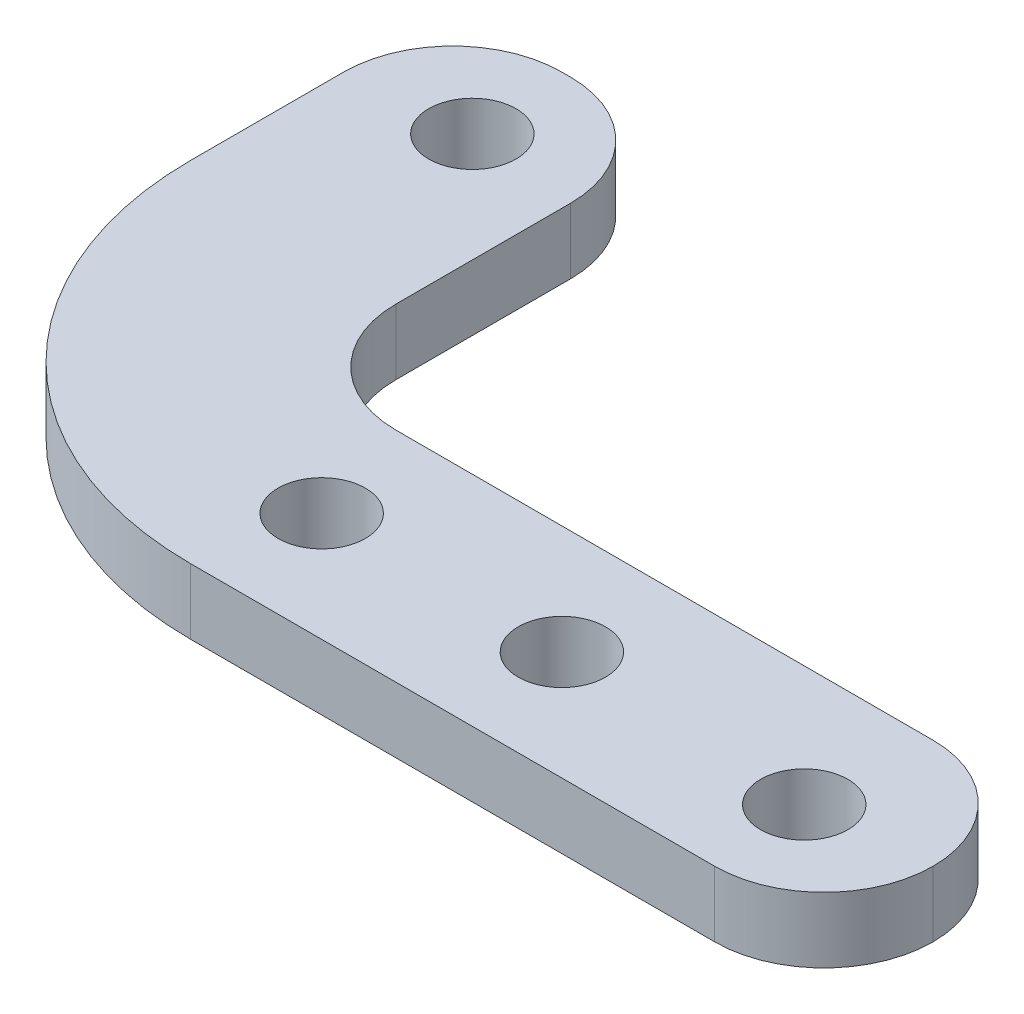
SolidWorks part; units mm, degrees
material "ABS PC"
ref_plane "Front Plane" through (0, 0, 0) normal (0, 0, 1) x (1, 0, 0)
ref_plane "Top Plane" through (0, 0, 0) normal (0, 1, 0) x (1, 0, 0)
ref_plane "Right Plane" through (0, 0, 0) normal (1, 0, 0) x (0, 0, -1)
sketch "Sketch1" plane through (0, 0, 0) normal (0, 1, 0) x (1, 0, 0)
  line L1 (22.5, -14) -> (-22.5, -14)
  line L2 (22.5, -14) -> (22.5, 14)
  line L3 (22.5, 14) -> (-22.5, 14)
  line L4 (-22.5, -14) -> (-22.5, 14)
  line L5 (22.5, -14) -> (-22.5, 14) construction
  line L6 (22.5, 14) -> (-22.5, -14) construction
  point P0 (0, 0)
  dimension "D1" = 28
  dimension "D2" = 45
extrude "Boss-Extrude1" add sketch "Sketch1" along normal blind 3
hole_wizard "Ø4.0 (4) Diameter Hole1" positions "Sketch2" profile "Sketch3" hole size "Ø4.0" standard "ANSI Metric" end condition through all
sketch "Sketch2" plane through (0, 3, 0) normal (0, 1, 0) x (1, 0, 0)
  line L1 (17.1, -9.5) -> (-17.1, -9.5)
  line L2 (17.1, -9.5) -> (17.1, 9.5)
  line L3 (17.1, 9.5) -> (-17.1, 9.5)
  line L4 (-17.1, -9.5) -> (-17.1, 9.5)
  line L5 (17.1, -9.5) -> (-17.1, 9.5) construction
  line L6 (17.1, 9.5) -> (-17.1, -9.5) construction
  line L7 (0, 14) -> (0, 0) construction
  line L8 (22.5, 14) -> (-22.5, 14) construction
  line L9 (0, 0) -> (0, -14) construction
  line L10 (-22.5, -14) -> (22.5, -14) construction
  point P2 (-17.1, 9.5)
  point P5 (17.1, -9.5)
  dimension "D1" = 19
  dimension "D2" = 34.2
sketch "Sketch3" plane through (-17.1, 3, -9.5) normal (1, 0, 0) x (0, 0, 1)
  line L0 (0, 0) -> (0, 3)
  line L1 (0, 3) -> (2, 3)
  line L2 (2, 3) -> (2, 0)
  line L5 (2, 0) -> (0, 0)
  line L11 (0, -6.35) -> (0, 107.95) construction
  dimension "Thru Hole Dia." = 4
  dimension "Thru Hole Depth" = 3
sketch "Sketch4" plane through (0, 3, 0) normal (0, 1, 0) x (1, 0, 0)
  line L0 (-22.5, -14) -> (22.5, -14) construction
  line L1 (9, -9) -> (-9, -9)
  line L2 (9, -9) -> (9, -14)
  line L3 (9, -14) -> (-9, -14)
  line L4 (-9, -9) -> (-9, -14)
  line L5 (9, -9) -> (-9, -14) construction
  line L6 (9, -14) -> (-9, -9) construction
  line L7 (0, -11.5) -> (0, 0) construction
  point P0 (0, -11.5)
  dimension "D1" = 18
  dimension "D2" = 5
extrude "Cut-Extrude1" [suppressed] cut sketch "Sketch4" against normal blind 3
hole_wizard "Ø4.0 (4) Diameter Hole2" positions "Sketch7" profile "Sketch8" hole size "Ø4.0" standard "ANSI Metric" end condition through all
sketch "Sketch7" plane through (0, 3, 0) normal (0, 1, 0) x (1, 0, 0)
  line L0 (0, 18.0075) -> (0, 15.2248) construction
  line L2 (-22.5, -14) -> (22.5, -14) construction
  point P0 (-5.5, -9)
  point P7 (5.5, -9)
  dimension "D1" = 11
  dimension "D2" = 5
sketch "Sketch8" plane through (-5.5, 3, 9) normal (1, 0, 0) x (0, 0, 1)
  line L0 (0, 0) -> (0, 3)
  line L1 (0, 3) -> (2, 3)
  line L2 (2, 3) -> (2, 0)
  line L5 (2, 0) -> (0, 0)
  line L11 (0, -6.35) -> (0, 107.95) construction
  dimension "Thru Hole Dia." = 4
  dimension "Thru Hole Depth" = 3
sketch "Sketch10" plane through (0, 3, 0) normal (0, 1, 0) x (1, 0, 0)
  line L0 (-12.1, 14) -> (-12.1, -4)
  line L1 (22.5, 14) -> (-22.5, 14) construction
  line L2 (-12.1, -4) -> (22.5, -4)
  line L3 (22.5, -14) -> (22.5, 14) construction
  line L4 (22.5, -4) -> (22.5, 14)
  line L5 (22.5, 14) -> (-12.1, 14)
  circle A0 centre (-17.1, 9.5) radius 2 construction
  circle A1 centre (5.5, -9) radius 2 construction
  dimension "D1" = 5
  dimension "D2" = 5
extrude "Cut-Extrude2" cut sketch "Sketch10" against normal blind 3
fillet "Fillet2" radius 5 5 edges at (22.5, 1.5, 4) (22.5, 1.5, 14) (-22.5, 1.5, -14) (-12.1, 1.5, -14) (-12.1, 1.5, 4)
fillet "Fillet3" radius 16 1 edges at (-22.5, 1.5, 14)
